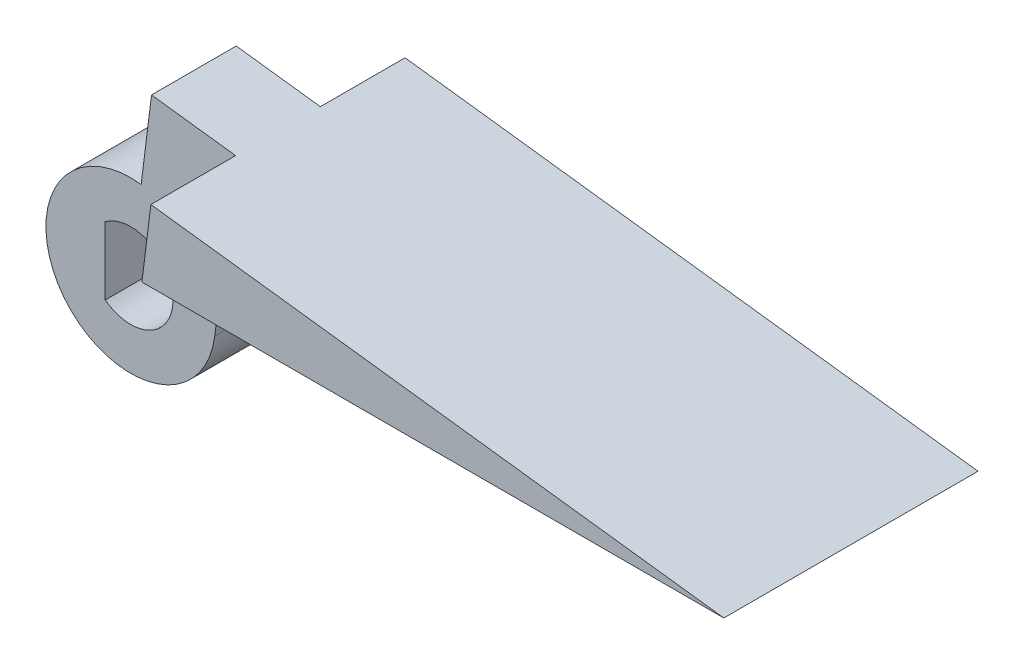
SolidWorks part; units mm, degrees
ref_plane "Front Plane" through (0, 0, 0) normal (0, 0, 1) x (1, 0, 0)
ref_plane "Top Plane" through (0, 0, 0) normal (0, 1, 0) x (1, 0, 0)
ref_plane "Right Plane" through (0, 0, 0) normal (1, 0, 0) x (0, 0, -1)
sketch "Sketch1" plane through (0, 0, 0) normal (0, 0, 1) x (1, 0, 0)
  line L0 (0, -6.35) -> (50.8, -6.35) construction
  line L6 (50.8, -6.35) -> (6.301, -0.7876) construction
  line L7 (6.301, 11.9124) -> (50.8, 6.35)
  line L8 (50.8, 6.35) -> (7.1932, 6.35)
  line L11 (0.7815, 12.6023) -> (6.301, 11.9124)
  line L12 (0, 6.35) -> (0.7815, 12.6023)
  line L13 (6.301, -0.7876) -> (7.1932, 6.35)
  circle A2 centre (0, 0) radius 3.175
  arc A5 (0, -6.35) -> (-6.301, 0.7876) centre (0, 0) cw
  arc A6 (0, -6.35) -> (6.301, -0.7876) centre (0, 0) ccw
  arc A8 (-6.301, 0.7876) -> (0, 6.35) centre (0, 0) cw
  point P10 (0, 0)
  point P11 (0, 0)
  point P14 (9.9392, 11.4576)
  dimension "D1" = 6.35
  dimension "D2" = 50.8
  dimension "D3" = 6.35
  dimension "D4" = 12.7
extrude "Boss-Extrude1" add sketch "Sketch1" along normal mid plane 19.05
sketch "Sketch2" plane through (0, 0, 9.525) normal (0, 0, 1) x (1, 0, 0)
  line L1 (7.1932, 21.1155) -> (-6.35, 21.1155)
  line L2 (-6.35, 21.1155) -> (-6.35, 0.2577)
  line L3 (-6.35, 0.2577) -> (-6.35, -6.35)
  line L4 (-6.35, -6.35) -> (7.1932, -6.35)
  line L5 (7.1932, -6.35) -> (7.1932, 6.35)
  line L7 (7.1932, 6.35) -> (8.9414, 20.3356)
  line L8 (6.301, -0.7876) -> (7.1932, 6.35) construction
  line L9 (8.9414, 20.3356) -> (7.1932, 21.1155)
  arc A5 (0, 6.35) -> (6.301, -0.7876) centre (0, 0) ccw construction
extrude "Cut-Extrude1" cut sketch "Sketch2" against normal blind 6.35
extrude "Cut-Extrude2" cut sketch "Sketch2<2>" along normal blind 6.35 from surface starting at face at (11.4329, 4.7762, -9.525)
sketch "Sketch2<2>" plane through (0, 0, 9.525) normal (0, 0, 1) x (1, 0, 0) same geometry as "Sketch2"
sketch "Sketch3" plane through (0, 0, 3.175) normal (0, 0, 1) x (1, 0, 0)
  line L1 (-1.905, 2.54) -> (-1.905, -2.54)
  arc A3 (-1.905, 2.54) -> (-1.905, -2.54) centre (0, 0) ccw
  circle A4 centre (0, 0) radius 3.175 construction
  dimension "D1" = 1.905
extrude "Boss-Extrude2" add sketch "Sketch3" against normal blind 6.35
sketch "Sketch4" plane through (0, 0, 3.175) normal (0, 0, 1) x (1, 0, 0)
  line L3 (0.7876, 6.301) -> (1.5631, 12.5046)
  line L4 (7.864, 11.717) -> (0.7815, 12.6023) construction
  line L5 (1.5631, 12.5046) -> (-1.5157, 12.8895)
  line L6 (-1.5157, 12.8895) -> (-2.3916, 5.8824)
  arc A1 (0, 6.35) -> (6.301, -0.7876) centre (0, 0) ccw construction
  arc A2 (0.7876, 6.301) -> (-2.3916, 5.8824) centre (0, 0) ccw
extrude "Cut-Extrude5" cut sketch "Sketch4" against normal through all both
